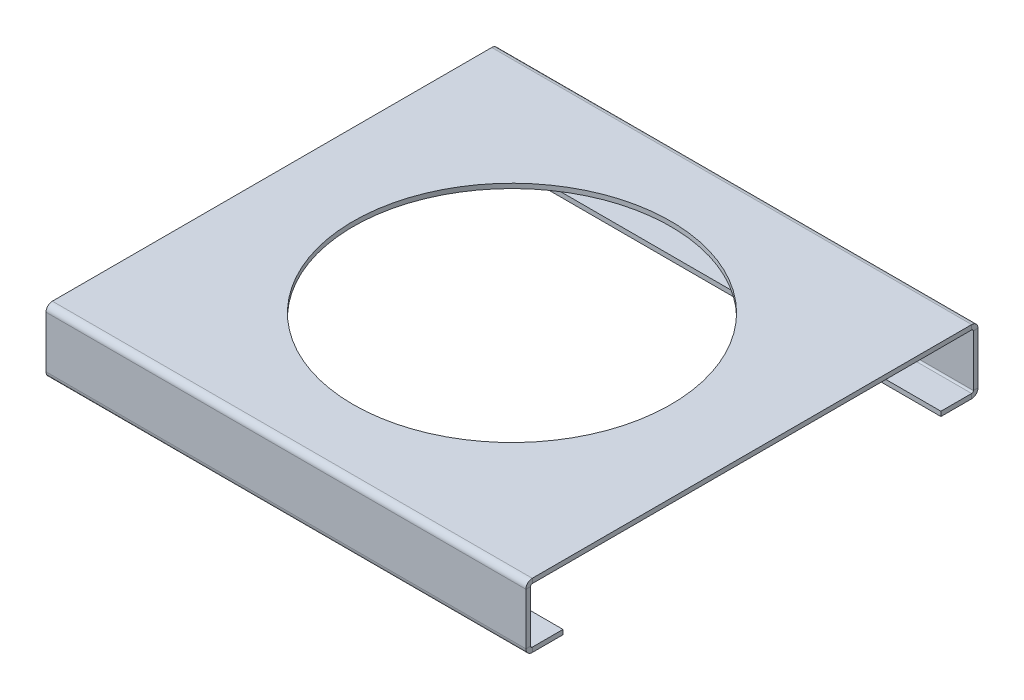
SolidWorks part; units mm, degrees
note: The reader was unsure of these and kept them because the rebuilt part matched: flange length of "Edge-Flange1", "Edge-Flange2".
ref_plane "Front Plane" through (0, 0, 0) normal (0, 0, 1) x (1, 0, 0)
ref_plane "Top Plane" through (0, 0, 0) normal (0, 1, 0) x (1, 0, 0)
ref_plane "Right Plane" through (0, 0, 0) normal (1, 0, 0) x (0, 0, -1)
sketch "Sketch3" plane through (0, 0, 0) normal (0, 1, 0) x (1, 0, 0)
  line L0 (102.1451, 97.3645) -> (-104.8549, 97.3645)
  line L1 (-104.8549, 97.3645) -> (-104.8549, -97.6355)
  line L2 (-104.8549, -97.6355) -> (102.1451, -97.6355)
  line L3 (102.1451, -97.6355) -> (102.1451, 97.3645)
base flange "Base-Flange1" sketch "Sketch3" thickness 2 reverse thickness direction no parameters "D1"=0.7366
edge flange "Edge-Flange1" sketch "Sketch12" flange profiles "Sketch12", "Sketch13" flange angle 90 flange length 25 flange position material inside bend radius 0.7366 thickness 2 relief rectangular parameters "D6"=10, "D8"=1
sketch "Sketch12" plane through (0, -2, 97.6355) normal (0, 0, 1) x (-1, 0, 0)
  line L0 (104.8549, 0) -> (-102.1451, 0) construction
  line L1 (104.8549, 0) -> (-102.1451, 0)
  line L2 (-102.1451, 0) -> (-102.1451, 23)
  line L3 (-102.1451, 23) -> (104.8549, 23)
  line L4 (104.8549, 23) -> (104.8549, 0)
sketch "Sketch13" plane through (0, -2, -97.3645) normal (0, 0, -1) x (1, 0, 0)
  line L0 (102.1451, 0) -> (-104.8549, 0) construction
  line L1 (102.1451, 0) -> (-104.8549, 0)
  line L2 (-104.8549, 0) -> (-104.8549, 23)
  line L3 (-104.8549, 23) -> (102.1451, 23)
  line L4 (102.1451, 23) -> (102.1451, 0)
bend "EdgeBend1" bend radius 0.7366 bend angle 90 parameters "D5"=1
bend "EdgeBend2" bend radius 0.7366 bend angle 90 parameters "D5"=2
sketch "Sketch14" plane through (0, 0, 0) normal (0, 1, 0) x (1, 0, 0)
  line L4 (-104.8549, -0.1355) -> (102.1451, -0.1355) construction
  line L5 (-104.8549, 94.6279) -> (102.1451, 94.6279)
  line L6 (-104.8549, 94.6279) -> (-104.8549, -94.8989)
  line L7 (-104.8549, -94.8989) -> (102.1451, -94.8989)
  line L8 (102.1451, 94.6279) -> (102.1451, -94.8989)
  line L9 (102.1451, -0.1355) -> (-1.3549, -94.8989) construction
  line L10 (-1.3549, -94.8989) -> (-1.3549, 94.6279) construction
  circle A0 centre (-1.3549, -0.1355) radius 68.5
  point P12 (-1.3549, -0.1355)
  point P13 (-1.3549, -0.1355)
  dimension "D1" = 137
extrude "Cut-Extrude1" cut sketch "Sketch14" against normal blind 2 contours A0 normal cut yes
edge flange "Edge-Flange2" sketch "Sketch19" flange profiles "Sketch19", "Sketch20" flange angle 90 flange length 16 flange position bend outside bend radius 0.7366 thickness 2 relief rectangular parameters "D6"=10, "D8"=1
sketch "Sketch19" plane through (0, -25, 95.6355) normal (0, -1, 0) x (-1, 0, 0)
  line L2 (-102.1451, 0) -> (-102.1451, 14)
  line L3 (-102.1451, 14) -> (104.8549, 14)
  line L4 (104.8549, 14) -> (104.8549, 0)
  line L7 (104.8549, 0) -> (-102.1451, 0) construction
  line L8 (104.8549, 0) -> (-102.1451, 0)
sketch "Sketch20" plane through (0, -25, -95.3645) normal (0, -1, 0) x (1, 0, 0)
  line L0 (102.1451, 0) -> (-104.8549, 0) construction
  line L1 (102.1451, 0) -> (-104.8549, 0)
  line L2 (-104.8549, 0) -> (-104.8549, 14)
  line L3 (-104.8549, 14) -> (102.1451, 14)
  line L4 (102.1451, 14) -> (102.1451, 0)
bend "EdgeBend3" bend radius 0.7366 bend angle 90 parameters "D5"=3
bend "EdgeBend4" bend radius 0.7366 bend angle 90 parameters "D5"=4
sketch "Bend-Lines1" [suppressed] plane through (0, 0, 0) normal (0, 1, 0) x (1, 0, 0)
sketch "Bounding-Box1" [suppressed] plane through (0, 0, 0) normal (0, 1, 0) x (1, 0, 0)
sheet metal parameters "Sheet-Metal3" thickness 2 parameters "D1"=0.7366
flat pattern "Flat-Pattern3" [suppressed]
sketch "Bend-Lines2" plane through (0, 0, 0) normal (0, 1, 0) x (1, 0, 0)
sketch3d "Bounding-Box2" [suppressed]
  line L0 (-102.1451, -97.6355, 0) -> (104.8549, -97.6355, 0) construction
  line L1 (-102.1451, 97.3645, 0) -> (104.8549, 97.3645, 0) construction
  line L2 (-102.1451, -97.6355, 0) -> (-102.1451, 97.3645, 0) construction
  line L3 (104.8549, -97.6355, 0) -> (104.8549, 97.3645, 0) construction
sheet metal parameters "Sheet-Metal4" thickness 2 parameters "D1"=0.7366
flat pattern "Flat-Pattern3"
sketch "Bend-Lines2" plane through (0, 0, 0) normal (0, 1, 0) x (1, 0, 0)
  line L0 (102.1451, 98.7284) -> (-104.8549, 98.7284) construction
  line L1 (-104.8549, -98.9994) -> (102.1451, -98.9994) construction
  line L2 (102.1451, 98.7284) -> (-104.8549, 98.7284) construction
  line L3 (-104.8549, -98.9994) -> (102.1451, -98.9994) construction
sketch3d "Bounding-Box2" [suppressed]
  line L0 (-104.8549, 122.3558, 0) -> (-104.8549, -122.6267, 0) construction
  line L1 (102.1451, 122.3558, 0) -> (102.1451, -122.6267, 0) construction
  line L2 (-104.8549, 122.3558, 0) -> (102.1451, 122.3558, 0) construction
  line L3 (-104.8549, -122.6267, 0) -> (102.1451, -122.6267, 0) construction
bend of the flat pattern "Flatten-<EdgeBend1>1"
bend of the flat pattern "Flatten-<EdgeBend2>1"
sheet metal parameters "Sheet-Metal5" thickness 2 parameters "D1"=0.7366
flat pattern "Flat-Pattern3"
sketch "Bend-Lines2" plane through (0, 0, 0) normal (0, 1, 0) x (1, 0, 0)
  line L0 (102.1451, 98.7284) -> (-104.8549, 98.7284) construction
  line L1 (-104.8549, -98.9994) -> (102.1451, -98.9994) construction
  line L2 (102.1451, 98.7284) -> (-104.8549, 98.7284) construction
  line L3 (-104.8549, -98.9994) -> (102.1451, -98.9994) construction
sketch3d "Bounding-Box2" [suppressed]
  line L0 (-104.8549, 122.3558, 0) -> (-104.8549, -122.6267, 0) construction
  line L1 (102.1451, 122.3558, 0) -> (102.1451, -122.6267, 0) construction
  line L2 (-104.8549, 122.3558, 0) -> (102.1451, 122.3558, 0) construction
  line L3 (-104.8549, -122.6267, 0) -> (102.1451, -122.6267, 0) construction
bend of the flat pattern "Flatten-<EdgeBend1>1"
bend of the flat pattern "Flatten-<EdgeBend2>1"
sheet metal parameters "Sheet-Metal6" thickness 2 parameters "D1"=0.7366
flat pattern "Flat-Pattern3"
sketch "Bend-Lines2" plane through (0, 0, 0) normal (0, 1, 0) x (1, 0, 0)
  line L0 (102.1451, 95.9918) -> (-104.8549, 95.9918) construction
  line L1 (-104.8549, -96.2628) -> (102.1451, -96.2628) construction
  line L2 (102.1451, 95.9918) -> (-104.8549, 95.9918) construction
  line L3 (-104.8549, -96.2628) -> (102.1451, -96.2628) construction
  line L4 (102.1451, 120.9831) -> (-104.8549, 120.9831) construction
  line L5 (-104.8549, -121.2541) -> (102.1451, -121.2541) construction
  line L6 (102.1451, 120.9831) -> (-104.8549, 120.9831) construction
  line L7 (-104.8549, -121.2541) -> (102.1451, -121.2541) construction
sketch3d "Bounding-Box2" [suppressed]
  line L0 (-104.8549, 135.6104, 0) -> (-104.8549, -135.8814, 0) construction
  line L1 (102.1451, 135.6104, 0) -> (102.1451, -135.8814, 0) construction
  line L2 (-104.8549, 135.6104, 0) -> (102.1451, 135.6104, 0) construction
  line L3 (-104.8549, -135.8814, 0) -> (102.1451, -135.8814, 0) construction
bend of the flat pattern "Flatten-<EdgeBend1>1"
bend of the flat pattern "Flatten-<EdgeBend2>1"
bend of the flat pattern "Flatten-<EdgeBend3>1"
bend of the flat pattern "Flatten-<EdgeBend4>1"
